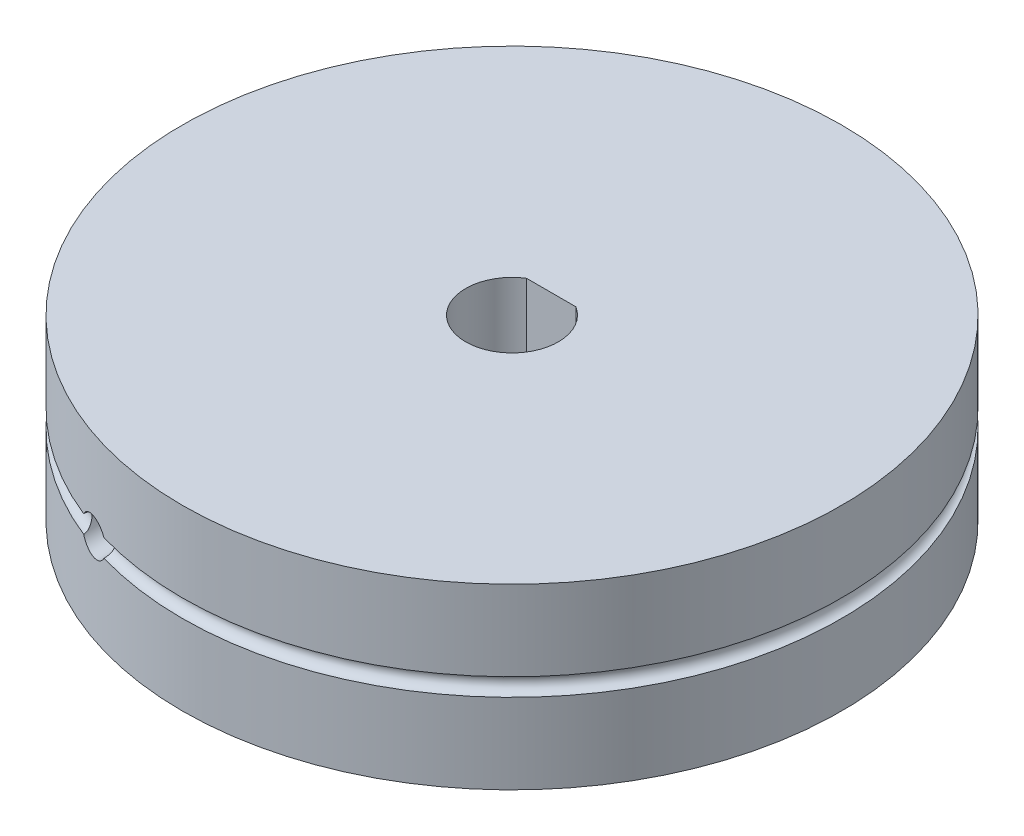
SolidWorks part; units mm, degrees
ref_plane "Front Plane" through (0, 0, 0) normal (0, 0, 1) x (1, 0, 0)
ref_plane "Top Plane" through (0, 0, 0) normal (0, 1, 0) x (1, 0, 0)
ref_plane "Right Plane" through (0, 0, 0) normal (1, 0, 0) x (0, 0, -1)
sketch "Sketch1" plane through (0, 0, 0) normal (0, 1, 0) x (1, 0, 0)
  circle A0 centre (0, 0) radius 18.5
  dimension "D1" = 37
extrude "Boss-Extrude1" add sketch "Sketch1" along normal blind 10
ref_axis "Axis1" through (0, 22.423, 0) along (0, -1, 0)
sketch "Sketch2" plane through (0, 0, 0) normal (0, 0, 1) x (1, 0, 0)
  line L1 (-18.5, 10) -> (-18.5, 0) construction
  circle A0 centre (-18.5, 5) radius 0.5
  point P2 (-18.5, 5)
  dimension "D1" = 1
revolve "Cut-Revolve1" cut sketch "Sketch2" angle 360 about axis through (0, 22.423, 0) along (0, -1, 0)
sketch "Sketch3" plane through (0, 10, 0) normal (0, 1, 0) x (1, 0, 0)
  line L0 (-1.3856, 2.2) -> (1.3856, 2.2)
  circle A0 centre (0, 0) radius 2.6
  point P5 (0, -2.6)
  dimension "D1" = 5.2
  dimension "D2" = 4.8
extrude "Cut-Extrude1" cut sketch "Sketch3" against normal up to next contours L0 A0 region at (0, 10, 0.0866)
sketch "Sketch4" plane through (0, 0, 0) normal (0, 0, 1) x (1, 0, 0)
  line L0 (-18.5, 5.5) -> (-18.5, 4.5) construction
  line L1 (0, 22.423) -> (0, 0) construction
  circle A0 centre (-6, 5) radius 1
  point P6 (-18.5, 5)
  dimension "D1" = 2
  dimension "D2" = 6
extrude "Cut-Extrude2" cut sketch "Sketch4" against normal up to next and the other way up to next
